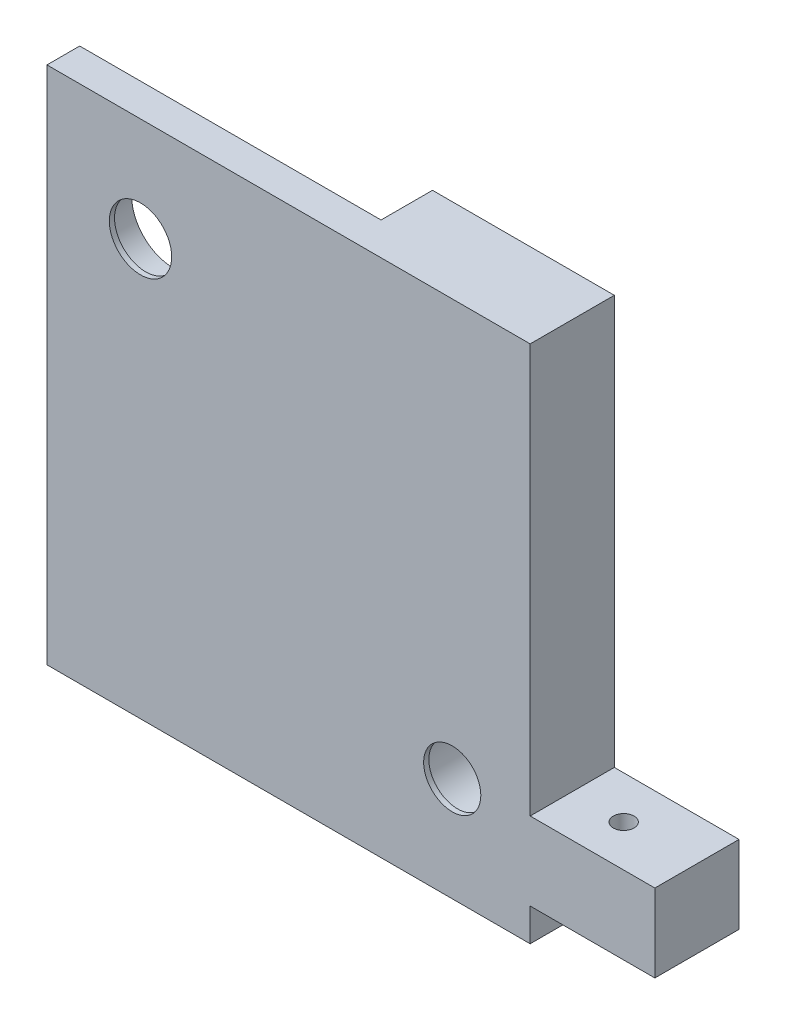
SolidWorks part; units mm, degrees
ref_plane "Front Plane" through (0, 0, 0) normal (0, 0, 1) x (1, 0, 0)
ref_plane "Top Plane" through (0, 0, 0) normal (0, 1, 0) x (1, 0, 0)
ref_plane "Right Plane" through (0, 0, 0) normal (1, 0, 0) x (0, 0, -1)
sketch "Sketch1" plane through (0, 0, 0) normal (0, 0, 1) x (1, 0, 0)
  line L1 (-76.1871, 64.9281) -> (16.8129, 64.9281)
  line L2 (-76.1871, 64.9281) -> (-76.1871, -35.0719)
  line L3 (-76.1871, -35.0719) -> (16.8129, -35.0719)
  line L4 (16.8129, 64.9281) -> (16.8129, -35.0719)
  dimension "D1" = 93
  dimension "D2" = 100
extrude "Boss-Extrude2" add sketch "Sketch1" along normal blind 6.3 contours L1 L4 L3 L2
sketch "Sketch3" plane through (0, 0, 0) normal (0, 0, -1) x (-1, 0, 0)
  line L0 (76.1871, -35.0719) -> (-16.8129, -35.0719) construction
  line L1 (-16.8129, 64.9281) -> (18.1871, 64.9281)
  line L2 (-16.8129, 64.9281) -> (-16.8129, -35.0719)
  line L3 (-16.8129, -35.0719) -> (18.1871, -35.0719)
  line L4 (18.1871, 64.9281) -> (18.1871, -35.0719)
  line L5 (-16.8129, 64.9281) -> (-16.8129, -35.0719) construction
  dimension "D1" = 0
  dimension "D2" = 0
  dimension "D3" = 35
  dimension "D4" = 100
extrude "Boss-Extrude3" add sketch "Sketch3" along normal blind 9.9
sketch "Sketch4" plane through (16.8129, 0, 0) normal (1, 0, 0) x (0, 0, -1)
  line L0 (-6.3, 64.9281) -> (-6.3, -35.0719) construction
  line L1 (-6.3, -13.7719) -> (9.9, -13.7719)
  line L2 (-6.3, -13.7719) -> (-6.3, -28.7719)
  line L3 (-6.3, -28.7719) -> (9.9, -28.7719)
  line L4 (9.9, -13.7719) -> (9.9, -28.7719)
  line L5 (9.9, 64.9281) -> (9.9, -35.0719) construction
  line L6 (-6.3, -35.0719) -> (9.9, -35.0719) construction
  dimension "D1" = 6.3
  dimension "D2" = 15
extrude "Boss-Extrude4" add sketch "Sketch4" along normal blind 24
sketch "Sketch5" plane through (0, -13.7719, 0) normal (0, 1, 0) x (1, 0, 0)
  line L0 (40.8129, -6.3) -> (16.8129, -6.3) construction
  line L2 (16.8129, 9.9) -> (16.8129, -6.3) construction
  circle A0 centre (26.8129, 1.7) radius 2
  dimension "D2" = 4
  dimension "D3" = 10
  dimension "D1" = 8
extrude "Cut-Extrude1" cut sketch "Sketch5" against normal blind 50
sketch "Sketch6" plane through (0, 0, -9.9) normal (0, 0, -1) x (-1, 0, 0)
  line L0 (-16.8129, -35.0719) -> (18.1871, -35.0719) construction
  line L1 (-16.8129, -28.7719) -> (-16.8129, -35.0719) construction
  circle A0 centre (-1.8129, -15.0719) radius 7.5
  dimension "D1" = 15
  dimension "D2" = 20
  dimension "D3" = 15
extrude "Cut-Extrude2" cut sketch "Sketch6" against normal blind 50
sketch "Sketch7" plane through (0, 0, 0) normal (0, 0, -1) x (-1, 0, 0)
  line L0 (76.1871, -35.0719) -> (18.1871, -35.0719) construction
  line L2 (-16.8129, 64.9281) -> (-16.8129, -13.7719) construction
  circle A0 centre (58.1871, 44.9281) radius 8
  point P6 (0, 0)
  point P7 (0, 0)
  dimension "D1" = 16
  dimension "D2" = 80
  dimension "D3" = 75
extrude "Cut-Extrude3" cut sketch "Sketch7" against normal blind 50
extrude "Extrude-Thin1" add sketch "Sketch7<2>" along normal blind 1 from surface thin starting at face at (-50.1871, 44.9281, 6.3) thin type one direction reverse wall 2
sketch "Sketch7<2>" plane through (0, 0, 0) normal (0, 0, -1) x (-1, 0, 0) same geometry as "Sketch7"
extrude "Extrude-Thin2" add sketch "Sketch6<2>" along normal blind 1 from surface thin starting at face at (9.3129, -15.0719, 6.3) thin type one direction reverse wall 2
sketch "Sketch6<2>" plane through (0, 0, -9.9) normal (0, 0, -1) x (-1, 0, 0) same geometry as "Sketch6"
